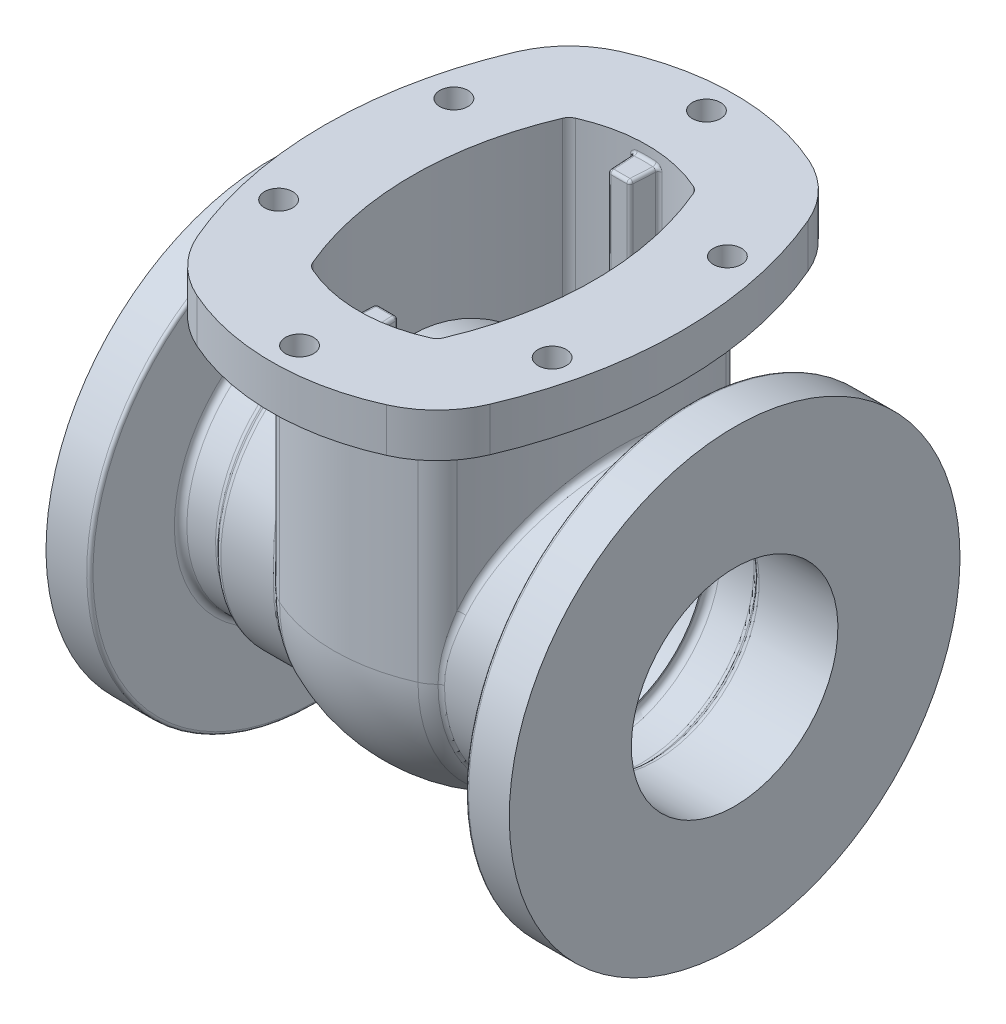
SolidWorks part; units mm, degrees
ref_plane "Front Plane" through (0, 0, 0) normal (0, 0, 1) x (1, 0, 0)
ref_plane "Top Plane" through (0, 0, 0) normal (0, 1, 0) x (1, 0, 0)
ref_plane "Right Plane" through (0, 0, 0) normal (1, 0, 0) x (0, 0, -1)
sketch "Sketch1" plane through (0, 0, 0) normal (0, 1, 0) x (1, 0, 0)
  line L0 (0, 73.025) -> (0, 0) construction
  line L1 (0, 0) -> (46.0375, 0) construction
  arc A0 (-29.9031, 66.6217) -> (29.9031, 66.6217) centre (0, 0) cw
  arc A1 (33.1473, -63.3113) -> (33.1473, 63.3113) centre (-115.8875, 0) ccw
  arc A2 (29.9031, 66.6217) -> (33.1473, 63.3113) centre (27.3028, 60.8285) cw
  arc A3 (-29.9031, 66.6217) -> (-33.1473, 63.3113) centre (-27.3028, 60.8285) ccw
  arc A4 (-33.1473, -63.3113) -> (-33.1473, 63.3113) centre (115.8875, 0) cw
  arc A5 (-29.9031, -66.6217) -> (-33.1473, -63.3113) centre (-27.3028, -60.8285) cw
  arc A6 (29.9031, -66.6217) -> (33.1473, -63.3113) centre (27.3028, -60.8285) ccw
  arc A7 (-29.9031, -66.6217) -> (29.9031, -66.6217) centre (0, 0) ccw
  arc A8 (-74.0588, -80.6909) -> (-74.0588, 80.6909) centre (115.8875, 0) cw
  arc A9 (-48.105, 107.1741) -> (-74.0588, 80.6909) centre (-27.3028, 60.8285) ccw
  arc A10 (-48.105, 107.1741) -> (48.105, 107.1741) centre (0, 0) cw
  arc A11 (48.105, 107.1741) -> (74.0588, 80.6909) centre (27.3028, 60.8285) cw
  arc A12 (74.0588, -80.6909) -> (74.0588, 80.6909) centre (-115.8875, 0) ccw
  arc A13 (48.105, -107.1741) -> (74.0588, -80.6909) centre (27.3028, -60.8285) ccw
  arc A14 (-48.105, -107.1741) -> (48.105, -107.1741) centre (0, 0) ccw
  arc A15 (-48.105, -107.1741) -> (-74.0588, -80.6909) centre (-27.3028, -60.8285) cw
  circle A16 centre (0, 103.1875) radius 7.1437
  arc A19 (69.3541, 44.45) -> (69.3541, -44.45) centre (-115.8875, 0) cw construction
  circle A20 centre (69.3541, 44.45) radius 7.1438
  circle A21 centre (69.3541, -44.45) radius 7.1438
  circle A22 centre (0, -103.1875) radius 7.1437
  circle A23 centre (-69.3541, 44.45) radius 7.1438
  arc A24 (-69.3541, 44.45) -> (-69.3541, -44.45) centre (115.8875, 0) ccw construction
  circle A25 centre (-69.3541, -44.45) radius 7.1438
  dimension "D1" = 73.025
  dimension "D2" = 161.925
  dimension "D4" = 6.35
  dimension "D6" = 103.1875
  dimension "D7" = 14.2875
  dimension "D8" = 190.5
  dimension "D3" = 115.8875
  dimension "D9" = 44.45
  dimension "D5" = 44.45
extrude "Boss-Extrude1" add sketch "Sketch1" along normal blind 22.225
sketch "Sketch3" plane through (0, 0, 0) normal (1, 0, 0) x (0, 0, -1)
  line L0 (-73.025, 0) -> (-73.025, -120.65)
  line L1 (-107.1741, 0) -> (-80.6909, 0) construction
  line L2 (0, 0) -> (0, -120.65) construction
  line L3 (-80.6909, 0) -> (80.6909, 0) construction
  line L4 (80.6909, 22.225) -> (-80.6909, 22.225) construction
  line L5 (73.025, 0) -> (73.025, -120.65)
  arc A0 (-73.025, -120.65) -> (73.025, -120.65) centre (0, -120.65) ccw
  circle A1 centre (0, -120.65) radius 51.5938
  dimension "D3" = 103.1875
  dimension "D1" = 142.875
  dimension "D2" = 73.025
sketch "Sketch4" plane through (0, 0, 0) normal (0, -1, 0) x (1, 0, 0)
  arc A0 (-29.9031, 66.6217) -> (-33.1473, 63.3113) centre (-27.3028, 60.8285) ccw construction
  arc A1 (-33.1473, 63.3113) -> (-33.1473, -63.3113) centre (115.8875, 0) ccw construction
  arc A2 (-33.1473, -63.3113) -> (-29.9031, -66.6217) centre (-27.3028, -60.8285) ccw construction
  arc A3 (29.9031, -66.6217) -> (33.1473, -63.3113) centre (27.3028, -60.8285) ccw construction
  arc A4 (-29.9031, -66.6217) -> (29.9031, -66.6217) centre (0, 0) ccw construction
  arc A5 (33.1473, -63.3113) -> (33.1473, 63.3113) centre (-115.8875, 0) ccw construction
  arc A6 (33.1473, 63.3113) -> (29.9031, 66.6217) centre (27.3028, 60.8285) ccw construction
  arc A7 (29.9031, 66.6217) -> (-29.9031, 66.6217) centre (0, 0) ccw construction
  arc A8 (-29.9031, 66.6217) -> (-33.1473, 63.3113) centre (-27.3028, 60.8285) ccw
  arc A9 (-33.1473, 63.3113) -> (-33.1473, -63.3113) centre (115.8875, 0) ccw
  arc A10 (-33.1473, -63.3113) -> (-29.9031, -66.6217) centre (-27.3028, -60.8285) ccw
  arc A11 (29.9031, -66.6217) -> (33.1473, -63.3113) centre (27.3028, -60.8285) ccw
  arc A12 (-29.9031, -66.6217) -> (29.9031, -66.6217) centre (0, 0) ccw
  arc A13 (33.1473, -63.3113) -> (33.1473, 63.3113) centre (-115.8875, 0) ccw
  arc A14 (33.1473, 63.3113) -> (29.9031, 66.6217) centre (27.3028, 60.8285) ccw
  arc A15 (29.9031, 66.6217) -> (-29.9031, 66.6217) centre (0, 0) ccw
  arc A16 (44.8363, -68.2769) -> (44.8363, 68.2769) centre (-115.8875, 0) ccw
  arc A17 (44.8363, 68.2769) -> (35.1036, 78.2081) centre (27.3028, 60.8285) ccw
  arc A18 (35.1036, 78.2081) -> (-35.1036, 78.2081) centre (0, 0) ccw
  arc A19 (-35.1036, 78.2081) -> (-44.8363, 68.2769) centre (-27.3028, 60.8285) ccw
  arc A20 (-44.8363, 68.2769) -> (-44.8363, -68.2769) centre (115.8875, 0) ccw
  arc A21 (-44.8363, -68.2769) -> (-35.1036, -78.2081) centre (-27.3028, -60.8285) ccw
  arc A22 (-35.1036, -78.2081) -> (35.1036, -78.2081) centre (0, 0) ccw
  arc A23 (35.1036, -78.2081) -> (44.8363, -68.2769) centre (27.3028, -60.8285) ccw
  dimension "D1" = 12.7
extrude "Boss-Extrude2" add sketch "Sketch4" along normal up to vertex (120.65 mm away) up to point (0, -120.65, 73.025)
sketch "Sketch5" plane through (0, -120.65, 0) normal (0, -1, 0) x (1, 0, 0)
  line L0 (58.7375, 0) -> (-58.7375, 0) construction
  line L1 (58.7375, 0) -> (46.0375, 0)
  line L2 (-46.0375, 0) -> (-58.7375, 0)
  arc A0 (44.8363, -68.2769) -> (44.8363, 68.2769) centre (-115.8875, 0) ccw construction
  arc A1 (-44.8363, 68.2769) -> (-44.8363, -68.2769) centre (115.8875, 0) ccw construction
  arc A2 (-29.9031, 66.6217) -> (-33.1473, 63.3113) centre (-27.3028, 60.8285) ccw construction
  arc A3 (-33.1473, 63.3113) -> (-33.1473, -63.3113) centre (115.8875, 0) ccw construction
  arc A4 (33.1473, -63.3113) -> (33.1473, 63.3113) centre (-115.8875, 0) ccw construction
  arc A5 (33.1473, 63.3113) -> (29.9031, 66.6217) centre (27.3028, 60.8285) ccw construction
  arc A6 (29.9031, 66.6217) -> (-29.9031, 66.6217) centre (0, 0) ccw construction
  arc A7 (-29.9031, 66.6217) -> (-33.1473, 63.3113) centre (-27.3028, 60.8285) ccw
  arc A8 (-33.1473, 63.3113) -> (-46.0375, 0) centre (115.8875, 0) ccw
  arc A9 (46.0375, 0) -> (33.1473, 63.3113) centre (-115.8875, 0) ccw
  arc A10 (35.1036, -78.2081) -> (44.8363, -68.2769) centre (27.3028, -60.8285) ccw
  arc A11 (44.8363, -68.2769) -> (44.8363, 68.2769) centre (-115.8875, 0) ccw
  arc A12 (44.8363, 68.2769) -> (35.1036, 78.2081) centre (27.3028, 60.8285) ccw
  arc A13 (35.1036, 78.2081) -> (-35.1036, 78.2081) centre (0, 0) ccw
  arc A14 (-35.1036, 78.2081) -> (-44.8363, 68.2769) centre (-27.3028, 60.8285) ccw
  arc A15 (-44.8363, 68.2769) -> (-44.8363, -68.2769) centre (115.8875, 0) ccw
  arc A16 (-44.8363, -68.2769) -> (-35.1036, -78.2081) centre (-27.3028, -60.8285) ccw
  arc A17 (-35.1036, -78.2081) -> (35.1036, -78.2081) centre (0, 0) ccw
  arc A19 (58.7375, 0) -> (44.8363, 68.2769) centre (-115.8875, 0) ccw
  arc A20 (44.8363, 68.2769) -> (35.1036, 78.2081) centre (27.3028, 60.8285) ccw
  arc A21 (35.1036, 78.2081) -> (-35.1036, 78.2081) centre (0, 0) ccw
  arc A22 (-35.1036, 78.2081) -> (-44.8363, 68.2769) centre (-27.3028, 60.8285) ccw
  arc A23 (-44.8363, 68.2769) -> (-58.7375, 0) centre (115.8875, 0) ccw
  arc A26 (33.1473, 63.3113) -> (29.9031, 66.6217) centre (27.3028, 60.8285) ccw
  arc A27 (29.9031, 66.6217) -> (-29.9031, 66.6217) centre (0, 0) ccw
  dimension "D1" = 0
revolve "Revolve1" add sketch "Sketch5" angle 180 about L0 reverse direction yes
sketch "Sketch6" plane through (0, 0, 0) normal (0, 0, 1) x (1, 0, 0)
  line L0 (0, -120.65) -> (117.475, -120.65) construction
  line L1 (-35.1036, -120.65) -> (35.1036, -120.65) construction
  line L2 (117.475, -234.95) -> (96.8375, -234.95)
  line L3 (95.25, -233.3625) -> (95.25, -188.9125)
  line L4 (95.25, -188.9125) -> (77.5151, -188.9125)
  line L5 (75.2701, -189.8424) -> (72.3674, -192.7451)
  line L6 (70.1224, -193.675) -> (41.9367, -193.675)
  line L7 (117.475, -234.95) -> (117.475, -173.0375)
  line L8 (117.475, -173.0375) -> (77.5151, -173.0375)
  line L9 (75.2701, -173.9674) -> (72.3674, -176.8701)
  line L10 (70.1224, -177.8) -> (49.1209, -177.8)
  line L11 (0, -120.65) -> (0, 0) construction
  line L12 (-48.105, 0) -> (48.105, 0) construction
  line L13 (-70.1224, -177.8) -> (-49.1209, -177.8)
  line L14 (-75.2701, -173.9674) -> (-72.3674, -176.8701)
  line L15 (-117.475, -173.0375) -> (-77.5151, -173.0375)
  line L16 (-117.475, -234.95) -> (-117.475, -173.0375)
  line L17 (-70.1224, -193.675) -> (-41.9367, -193.675)
  line L18 (-75.2701, -189.8424) -> (-72.3674, -192.7451)
  line L19 (-95.25, -188.9125) -> (-77.5151, -188.9125)
  line L20 (-95.25, -233.3625) -> (-95.25, -188.9125)
  line L21 (-117.475, -234.95) -> (-96.8375, -234.95)
  line L22 (41.9367, -193.675) -> (-41.9367, -193.675)
  line L23 (49.1209, -177.8) -> (-49.1209, -177.8)
  arc A0 (44.8363, -188.9269) -> (58.7375, -120.65) centre (-115.8875, -120.65) ccw construction
  arc A1 (-58.7375, -120.65) -> (-44.8363, -188.9269) centre (115.8875, -120.65) ccw construction
  arc A2 (-44.8363, -188.9269) -> (-35.1036, -198.8581) centre (-27.3028, -181.4785) ccw construction
  arc A3 (35.1036, -198.8581) -> (44.8363, -188.9269) centre (27.3028, -181.4785) ccw construction
  arc A4 (-58.7375, -120.65) -> (-44.8363, -188.9269) centre (115.8875, -120.65) ccw
  arc A5 (-44.8363, -188.9269) -> (-35.1036, -198.8581) centre (-27.3028, -181.4785) ccw
  arc A6 (44.8363, -188.9269) -> (58.7375, -120.65) centre (-115.8875, -120.65) ccw
  arc A7 (35.1036, -198.8581) -> (44.8363, -188.9269) centre (27.3028, -181.4785) ccw
  arc A8 (96.8375, -234.95) -> (95.25, -233.3625) centre (96.8375, -233.3625) cw
  arc A9 (77.5151, -173.0375) -> (75.2701, -173.9674) centre (77.5151, -176.2125) ccw
  arc A10 (72.3674, -176.8701) -> (70.1224, -177.8) centre (70.1224, -174.625) cw
  arc A11 (72.3674, -192.7451) -> (70.1224, -193.675) centre (70.1224, -190.5) cw
  arc A12 (77.5151, -188.9125) -> (75.2701, -189.8424) centre (77.5151, -192.0875) ccw
  arc A13 (-77.5151, -188.9125) -> (-75.2701, -189.8424) centre (-77.5151, -192.0875) cw
  arc A14 (-72.3674, -192.7451) -> (-70.1224, -193.675) centre (-70.1224, -190.5) ccw
  arc A15 (-72.3674, -176.8701) -> (-70.1224, -177.8) centre (-70.1224, -174.625) ccw
  arc A16 (-77.5151, -173.0375) -> (-75.2701, -173.9674) centre (-77.5151, -176.2125) cw
  arc A17 (-96.8375, -234.95) -> (-95.25, -233.3625) centre (-96.8375, -233.3625) ccw
  arc A18 (-35.1036, -198.8581) -> (-44.8363, -188.9269) centre (-27.3028, -181.4785) cw
  point P42 (95.25, -234.95)
  point P45 (76.2, -173.0375)
  point P48 (71.4375, -177.8)
  point P51 (71.4375, -193.675)
  point P54 (76.2, -188.9125)
  point P63 (-76.2, -188.9125)
  point P64 (-71.4375, -193.675)
  point P65 (-71.4375, -177.8)
  point P66 (-76.2, -173.0375)
  point P67 (-95.25, -234.95)
  dimension "D10" = 1.5875
  dimension "D11" = 3.175
  dimension "D2" = 114.3
  dimension "D3" = 22.225
  dimension "D4" = 19.05
  dimension "D5" = 15.875
  dimension "D6" = 45
  dimension "D7" = 4.7625
  dimension "D8" = 15.875
  dimension "D9" = 52.3875
  dimension "D12" = 117.475
revolve "Revolve2" add sketch "Sketch6" angle 360 about L0 region at (107.1562, -233.9733, 0) region at (-47.9851, -183.751, 0)
extrude "Cut-Extrude3" cut sketch "Sketch3" against normal through all both and the other way through all contours A1 region at (0, -120.65, 0)
fillet "Fillet1" radius 3.175 4 edges at (58.5076, -64.2063, -8.9574) (-58.5076, -64.2063, -8.9574) (49.1209, -177.8, 0) (-49.1209, -177.8, 0)
sketch "Sketch10" plane through (0, 0, 0) normal (1, 0, 0) x (0, 0, -1)
  line L0 (73.025, -120.65) -> (-73.025, -120.65) construction
  circle A0 centre (0, -120.65) radius 73.025
  circle A1 centre (0, -120.65) radius 73.025 construction
  circle A2 centre (0, -120.65) radius 60.325
  dimension "D1" = 12.7
extrude "Boss-Extrude3" add sketch "Sketch10" against normal up to body and the other way up to body separate body
sketch "Sketch11" plane through (0, 0, 0) normal (0, 0, 1) x (1, 0, 0)
  line L0 (0, -206.375) -> (0, 22.225) construction
  line L1 (48.105, 22.225) -> (-48.105, 22.225) construction
  line L2 (19.2368, -191.0957) -> (37.8999, 22.225)
  line L3 (25.4, -120.65) -> (0, -120.65) construction
  line L4 (37.8999, 22.225) -> (-37.8999, 22.225)
  line L5 (-19.2368, -191.0957) -> (-37.8999, 22.225)
  arc A0 (-35.1036, -198.8581) -> (35.1036, -198.8581) centre (0, -120.65) ccw construction
  arc A1 (19.2368, -191.0957) -> (-19.2368, -191.0957) centre (0, -120.65) cw
  dimension "D4" = 73.025
  dimension "D1" = 142.875
  dimension "D2" = 25.4
  dimension "D3" = 5
extrude "Cut-Extrude4" cut sketch "Sketch11" against normal up to surface and the other way up to surface up to face at (0, -87.5502, -3.0933) other way up to face at (0, -87.5502, -3.0933)
ref_plane "Plane4" through (0, 15.875, 0) normal (0, 1, 0) x (1, 0, 0)
sketch "Sketch15" plane through (0, 15.875, 0) normal (0, 1, 0) x (1, 0, 0)
  line L0 (0, 73.025) -> (0, -73.025) construction
  line L1 (5.5563, 58.7375) -> (-5.5562, 58.7375)
  line L2 (-5.5562, 58.7375) -> (-6.35, 72.7484)
  line L3 (5.5563, 58.7375) -> (6.35, 72.7484)
  line L4 (-46.0375, 0) -> (46.0375, 0) construction
  line L5 (5.5562, -58.7375) -> (6.35, -72.7484)
  line L6 (-5.5563, -58.7375) -> (-6.35, -72.7484)
  line L7 (5.5562, -58.7375) -> (-5.5563, -58.7375)
  line L8 (-6.35, -72.7484) -> (-6.35, -74.3359)
  line L9 (-6.35, -74.3359) -> (6.35, -74.3359)
  line L10 (6.35, -74.3359) -> (6.35, -72.7484)
  line L11 (-6.35, 72.7484) -> (-6.35, 74.3359)
  line L12 (-6.35, 74.3359) -> (6.35, 74.3359)
  line L13 (6.35, 74.3359) -> (6.35, 72.7484)
  arc A0 (29.9031, 66.6217) -> (-29.9031, 66.6217) centre (0, 0) ccw construction
  arc A2 (-33.1473, 63.3113) -> (-33.1473, -63.3113) centre (115.8875, 0) ccw construction
  arc A4 (33.1473, -63.3113) -> (33.1473, 63.3113) centre (-115.8875, 0) ccw construction
  point P11 (0, 58.7375)
  point P23 (0, -58.7375)
  dimension "D1" = 5.5562
  dimension "D3" = 6.35
  dimension "D2" = 14.2875
  dimension "D4" = 1.5875
extrude "Boss-Extrude5" add sketch "Sketch15" against normal blind 146.05 contours L11 L12 L13 L3 L1 L2 | L10 L5 L7 L6 L8 L9
fillet "Fillet3" radius 1.5875 22 edges at (-5.9433, -130.175, 65.5693) (5.9433, -130.175, 65.5693) (0, -130.175, 58.7375) (-5.9433, -130.175, -65.5693) (5.9433, -130.175, -65.5693) (0, -130.175, -58.7375) (5.9531, 15.875, -65.7429) (0, 15.875, -58.7375) (-5.9531, 15.875, -65.7429) (-5.9531, 15.875, 65.7429) (5.9531, 15.875, 65.7429) (0, 15.875, 58.7375) (5.5562, -57.15, 58.7375) (-5.5563, -57.15, 58.7375) (5.5563, -57.15, -58.7375) (-5.5562, -57.15, -58.7375) (0, 15.875, -73.025) (0, 15.875, 73.025) (6.35, -49.2125, 72.7484) (-6.35, -49.2125, 72.7484) (6.35, -49.2125, -72.7484) (-6.35, -49.2125, -72.7484)
fillet "Fillet4" radius 3.175 10 edges at (-41.9367, -193.675, 0) (41.9367, -193.675, 0) (95.25, -188.9125, 0) (-95.25, -188.9125, 0) (-58.1888, -48.9471, -13.8328) (58.1888, -48.9471, -13.8328)
